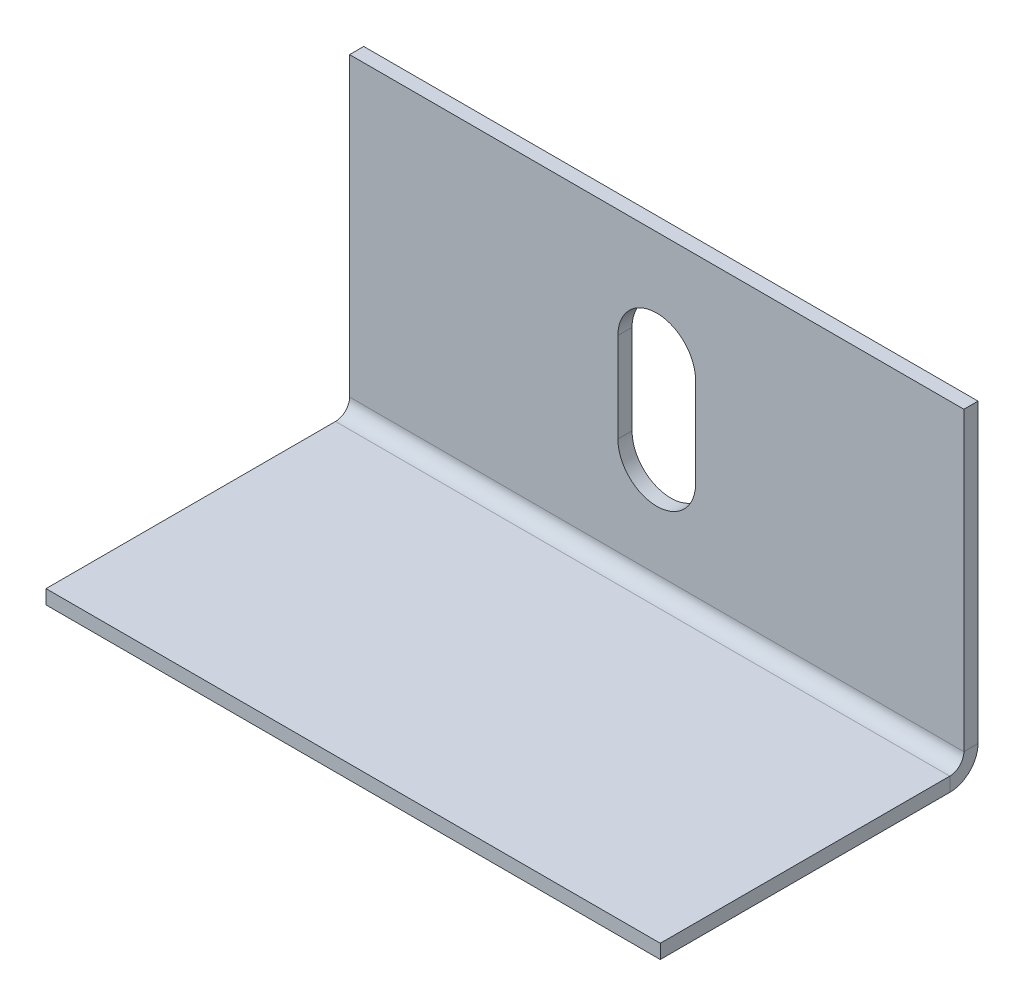
SolidWorks part; units mm, degrees
note: The reader was unsure of these and kept them because the rebuilt part matched: flange length of "Edge-Flange1".
material "ASTM A36 Steel"
ref_plane "Front Plane" through (0, 0, 0) normal (0, 0, 1) x (1, 0, 0)
ref_plane "Top Plane" through (0, 0, 0) normal (0, 1, 0) x (1, 0, 0)
ref_plane "Right Plane" through (0, 0, 0) normal (1, 0, 0) x (0, 0, -1)
sketch "Sketch1" plane through (0, 0, 0) normal (0, 1, 0) x (1, 0, 0)
  line L1 (-43.5, -21.5) -> (43.5, -21.5)
  line L2 (-43.5, -21.5) -> (-43.5, 21.5)
  line L3 (-43.5, 21.5) -> (43.5, 21.5)
  line L4 (43.5, -21.5) -> (43.5, 21.5)
  line L5 (-43.5, -21.5) -> (43.5, 21.5) construction
  line L6 (-43.5, 21.5) -> (43.5, -21.5) construction
  point P0 (0, 0)
base flange "Base-Flange1" sketch "Sketch1" thickness 2 reverse thickness direction no parameters "D1"=2
edge flange "Edge-Flange1" sketch "Sketch8" flange angle 90 flange length 44 flange position material outside bend radius 2 thickness 2 relief rectangular parameters "D6"=10
sketch "Sketch8" plane through (0, 0, -21.5) normal (0, 0, -1) x (-1, 0, 0)
  line L0 (-43.5, 0) -> (43.5, 0) construction
  line L1 (-43.5, 0) -> (43.5, 0)
  line L2 (-43.5, 0) -> (-43.5, 44)
  line L3 (-43.5, 44) -> (43.5, 44)
  line L4 (43.5, 44) -> (43.5, 0)
bend "EdgeBend1" bend radius 2 bend angle 90 parameters "D5"=1
sketch "Sketch9" plane through (0, 0, -23.5) normal (0, 0, -1) x (-1, 0, 0)
  line L2 (0, 28.5487) -> (0, 15.8487) construction
  line L3 (5.5, 28.5487) -> (5.5, 15.8487)
  line L4 (-5.5, 28.5487) -> (-5.5, 15.8487)
  arc A0 (5.5, 28.5487) -> (-5.5, 28.5487) centre (0, 28.5487) ccw
  arc A1 (-5.5, 15.8487) -> (5.5, 15.8487) centre (0, 15.8487) ccw
  point P5 (0, 22.1987)
extrude "Cut-Extrude1" cut sketch "Sketch9" against normal blind 10
sketch "Bend-Lines1" [suppressed] plane through (0, 0, 0) normal (0, 1, 0) x (1, 0, 0)
sketch "Bounding-Box1" [suppressed] plane through (0, 0, 0) normal (0, 1, 0) x (1, 0, 0)
sheet metal parameters "Sheet-Metal1" thickness 2 parameters "D1"=2
flat pattern "Flat-Pattern1" [suppressed]
sketch "Bend-Lines2" plane through (0, 0, 0) normal (0, 1, 0) x (1, 0, 0)
sketch3d "Bounding-Box2" [suppressed]
  line L0 (-43.5, 21.5, 0) -> (43.5, 21.5, 0) construction
  line L1 (-43.5, -21.5, 0) -> (43.5, -21.5, 0) construction
  line L2 (-43.5, 21.5, 0) -> (-43.5, -21.5, 0) construction
  line L3 (43.5, 21.5, 0) -> (43.5, -21.5, 0) construction
sheet metal parameters "Sheet-Metal2" thickness 2 parameters "D1"=2
flat pattern "Flat-Pattern1"
sketch "Bend-Lines2" plane through (0, 0, 0) normal (0, 1, 0) x (1, 0, 0)
  line L0 (43.5, 21.8562) -> (-43.5, 21.8562) construction
  line L1 (43.5, 21.8562) -> (-43.5, 21.8562) construction
sketch3d "Bounding-Box2" [suppressed]
  line L0 (-43.5, -21.5, 0) -> (-43.5, 66.2124, 0) construction
  line L1 (43.5, -21.5, 0) -> (43.5, 66.2124, 0) construction
  line L2 (-43.5, -21.5, 0) -> (43.5, -21.5, 0) construction
  line L3 (-43.5, 66.2124, 0) -> (43.5, 66.2124, 0) construction
bend of the flat pattern "Flatten-<EdgeBend1>1"
sheet metal parameters "Sheet-Metal3" thickness 2 parameters "D1"=2
flat pattern "Flat-Pattern1"
sketch "Bend-Lines2" plane through (0, 0, 0) normal (0, 1, 0) x (1, 0, 0)
  line L0 (43.5, 21.8562) -> (-43.5, 21.8562) construction
  line L1 (43.5, 21.8562) -> (-43.5, 21.8562) construction
sketch3d "Bounding-Box2" [suppressed]
  line L0 (-43.5, -21.5, 0) -> (-43.5, 66.2124, 0) construction
  line L1 (43.5, -21.5, 0) -> (43.5, 66.2124, 0) construction
  line L2 (-43.5, -21.5, 0) -> (43.5, -21.5, 0) construction
  line L3 (-43.5, 66.2124, 0) -> (43.5, 66.2124, 0) construction
bend of the flat pattern "Flatten-<EdgeBend1>1"
